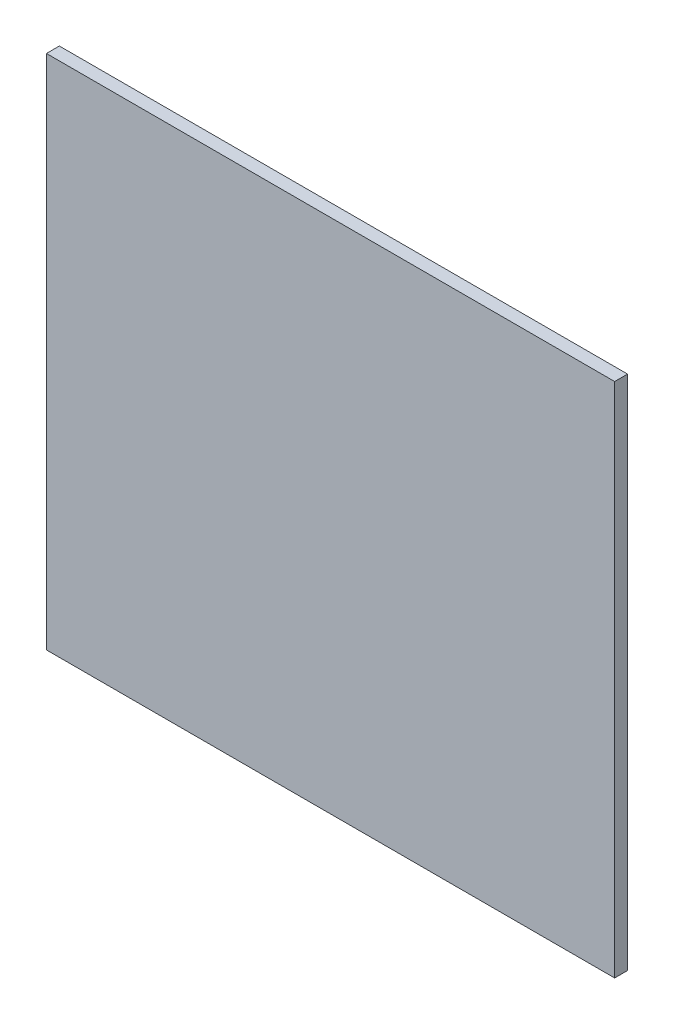
SolidWorks part; units mm, degrees
ref_plane "Front Plane" through (0, 0, 0) normal (0, 0, 1) x (1, 0, 0)
ref_plane "Top Plane" through (0, 0, 0) normal (0, 1, 0) x (1, 0, 0)
ref_plane "Right Plane" through (0, 0, 0) normal (1, 0, 0) x (0, 0, -1)
sketch "Sketch1" plane through (0, 0, 0) normal (0, 0, 1) x (1, 0, 0)
  line L1 (-69.85, 63.5) -> (69.85, 63.5)
  line L2 (-69.85, 63.5) -> (-69.85, -63.5)
  line L3 (-69.85, -63.5) -> (69.85, -63.5)
  line L4 (69.85, 63.5) -> (69.85, -63.5)
  line L5 (-69.85, 63.5) -> (69.85, -63.5) construction
  line L6 (-69.85, -63.5) -> (69.85, 63.5) construction
  line L10 (58.2701, -50.8698) -> (58.2701, 50.8698)
  line L11 (58.2701, 50.8698) -> (-58.2701, 50.8698)
  line L12 (-58.2701, 50.8698) -> (-58.2701, -50.8698)
  line L13 (-58.2701, -50.8698) -> (58.2701, -50.8698)
  line L14 (58.2701, -50.8698) -> (58.2701, 50.8698) construction
  line L15 (58.2701, 50.8698) -> (-58.2701, 50.8698)
  line L16 (-58.2701, 50.8698) -> (-58.2701, -50.8698)
  line L17 (-58.2701, -50.8698) -> (58.2701, -50.8698)
  point P0 (0, 0)
  point P8 (67.4889, 56.8008)
  dimension "D2" = 116.5403
  dimension "D3" = 101.7397
  dimension "D4" = 127
  dimension "D5" = 139.7
  dimension "D1" = 0
extrude "Boss-Extrude1" add sketch "Sketch1" along normal blind 3.175 contours L2 L1 L4 L3
